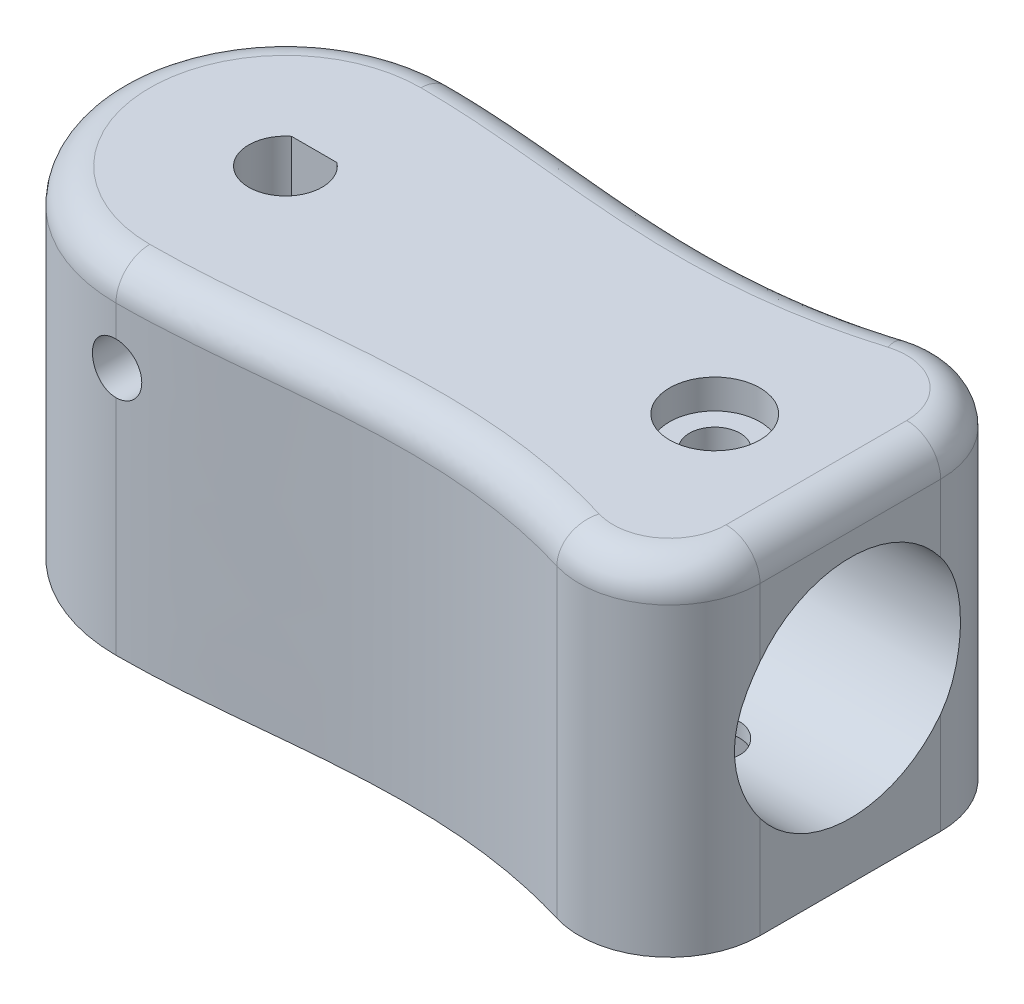
SolidWorks part; units mm, degrees
ref_plane "Front Plane" through (0, 0, 0) normal (0, 0, 1) x (1, 0, 0)
ref_plane "Top Plane" through (0, 0, 0) normal (0, 1, 0) x (1, 0, 0)
ref_plane "Right Plane" through (0, 0, 0) normal (1, 0, 0) x (0, 0, -1)
sketch "Sketch1" plane through (0, 0, 0) normal (0, 1, 0) x (1, 0, 0)
  line L1 (0, 0) -> (65, 0)
  line L2 (0, 0) -> (0, 40)
  line L3 (0, 40) -> (65, 40)
  line L4 (65, 0) -> (65, 40)
  dimension "D1" = 65
  dimension "D2" = 40
extrude "Boss-Extrude1" add sketch "Sketch1" along normal blind 30
sketch "Sketch2" plane through (0, 30, 0) normal (0, 1, 0) x (1, 0, 0)
  line L0 (0, 20) -> (65, 20) construction
  line L1 (0, 40) -> (0, 0) construction
  line L2 (65, 0) -> (65, 40) construction
  line L3 (32.5, 40) -> (32.5, 0) construction
  line L4 (65, 40) -> (0, 40) construction
  line L5 (0, 0) -> (65, 0) construction
  line L6 (15, 22.55) -> (15, 16.75) construction
  line L8 (0, 40) -> (0, 0)
  line L11 (12.9851, 22.55) -> (17.0149, 22.55)
  line L12 (26.5228, 35) -> (3.4274, 35) construction
  line L20 (0, 40) -> (0, 0)
  line L21 (0, 0) -> (65, 0)
  line L22 (65, 0) -> (65, 40)
  line L23 (65, 40) -> (0, 40)
  line L24 (0, 40) -> (0, 0)
  line L25 (0, 0) -> (65, 0)
  line L26 (65, 0) -> (65, 40)
  line L27 (65, 40) -> (0, 40)
  circle A0 centre (15, 20) radius 3.25
  circle A1 centre (53, 20) radius 2
  circle A3 centre (15, 20) radius 15
  spline S0 degree 3 poles (15, 35) (30.7585, 35) (45.016, 29.2369) (65, 40) knots 0 0 0 0 1 1 1 1
  spline S1 degree 3 poles (15, 5) (30.7585, 5) (45.016, 10.7631) (65, 0) knots 0 0 0 0 1 1 1 1
  point P21 (49.1925, 31.8398)
  point P24 (0, 0)
  point P25 (46.2539, 33.8689)
  point P34 (0, 0)
  line M8 (0, 40) -> (0, 0)
  line M9 (0, 0) -> (65, 0)
  line M11 (65, 40) -> (0, 40)
  dimension "D1" = 6.5
  dimension "D5" = 4
  dimension "D4" = 31.142
  dimension "D2" = 15
  dimension "D3" = 5.8
  dimension "D6" = 12
  dimension "D12" = 0
sketch "Sketch3" plane through (65, 0, 0) normal (1, 0, 0) x (0, 0, -1)
  line L0 (0, 15) -> (40, 15) construction
  line L1 (0, 30) -> (0, 0) construction
  line L2 (40, 30) -> (40, 0) construction
  line L3 (20, 30) -> (20, 0) construction
  line L4 (0, 30) -> (40, 30) construction
  line L5 (0, 0) -> (40, 0) construction
  line L7 (15, 30) -> (0, 30)
  line L8 (0, 30) -> (0, 0)
  line L9 (0, 0) -> (15, 0)
  circle A0 centre (20, 15) radius 10
  dimension "D1" = 20
extrude "Cut-Extrude2" cut sketch "Sketch3" against normal blind 35 contours A0 region at (65, 15, -20)
hole_wizard "CBORE for M4 Cheese Head Screw1" positions "Sketch4" profile "Sketch5" counterbore size "M4" standard "AS" end condition through all
sketch "Sketch4" plane through (0, 30, 0) normal (0, 1, 0) x (1, 0, 0)
  point P0 (53, 20)
sketch "Sketch5" plane through (53, 30, -20) normal (1, 0, 0) x (0, 0, 1)
  line L0 (0, 0) -> (0, 30)
  line L1 (0, 30) -> (2.25, 30)
  line L3 (2.25, 30) -> (2.25, 2.6)
  line L4 (2.25, 2.6) -> (4, 2.6)
  line L5 (4, 2.6) -> (4, 0)
  line L7 (4, 0) -> (0, 0)
  line L11 (0, -6.35) -> (0, 107.95) construction
  dimension "Thru Hole Dia." = 4.5
  dimension "Thru Hole Depth" = 30
  dimension "C'Bore Dia." = 8
  dimension "C'Bore Depth" = 2.6
sketch "Sketch10" plane through (0, 0, 0) normal (0, -1, 0) x (1, 0, 0)
  line L0 (53, -20) -> (53, -15.6699) construction
  line L1 (53, -15.6699) -> (49.25, -17.8349)
  line L2 (49.25, -17.8349) -> (49.25, -22.1651)
  line L3 (49.25, -22.1651) -> (53, -24.3301)
  line L4 (53, -24.3301) -> (56.75, -22.1651)
  line L5 (56.75, -22.1651) -> (56.75, -17.8349)
  line L6 (56.75, -17.8349) -> (53, -15.6699)
  circle A0 centre (53, -20) radius 2.25 construction
  circle A1 centre (53, -20) radius 2.25
  circle A2 centre (53, -20) radius 3.75 construction
  dimension "D1" = 7.5
extrude "Cut-Extrude8" cut sketch "Sketch10" against normal blind 4
extrude "Cut-Extrude9" cut sketch "Sketch2" against normal blind 15 contours L11 A0 region at (15, 30, -19.8255)
extrude "Cut-Extrude10" cut sketch "Sketch2<7>" against normal through all contours A3 S0 M11 M8 | S1 A3 L24 M9 region at (27.0713, 30, -36.5546) region at (27.0713, 30, -3.4454)
sketch "Sketch2<7>" plane through (0, 30, 0) normal (0, 1, 0) x (1, 0, 0) same geometry as "Sketch2"
fillet "Fillet9" radius 8 2 edges at (65, 15, 0) (65, 15, -40)
ref_plane "Plane1" through (0, 0, -35) normal (0, 0, 1) x (1, 0, 0)
sketch "Sketch12" plane through (0, 0, -35) normal (0, 0, 1) x (1, 0, 0)
  line L0 (15, 0) -> (15, 30) construction
  line L1 (15, 0) -> (15, 30) construction
  line L3 (18.7, 24.1362) -> (15, 26.2724)
  line L4 (15, 26.2724) -> (11.3, 24.1362)
  line L5 (11.3, 24.1362) -> (11.3, 19.8638)
  line L6 (11.3, 19.8638) -> (15, 17.7276)
  line L7 (15, 17.7276) -> (18.7, 19.8638)
  line L8 (18.7, 19.8638) -> (18.7, 24.1362)
  circle A0 centre (15, 22) radius 3.7 construction
  circle A1 centre (15, 22) radius 2.25
  dimension "D1" = 7.4
  dimension "D3" = 4.5
  dimension "D2" = 8
extrude "Cut-Extrude11" cut sketch "Sketch12" along normal blind 8 contours L7 L8 L3 L4 L5 L6 A1 | A1 region at (18.587, 22, -35) region at (15, 22, -35)
extrude "Cut-Extrude12" cut sketch "Sketch12<3>" along normal through all contours A1 region at (15, 22, -35)
sketch "Sketch12<3>" plane through (0, 0, -35) normal (0, 0, 1) x (1, 0, 0) same geometry as "Sketch12"
fillet "Fillet10" radius 3 6 edges at (0, 30, -20) (61.7643, 30, -34.4216) (65, 30, -20) (61.7643, 30, -5.5784)
